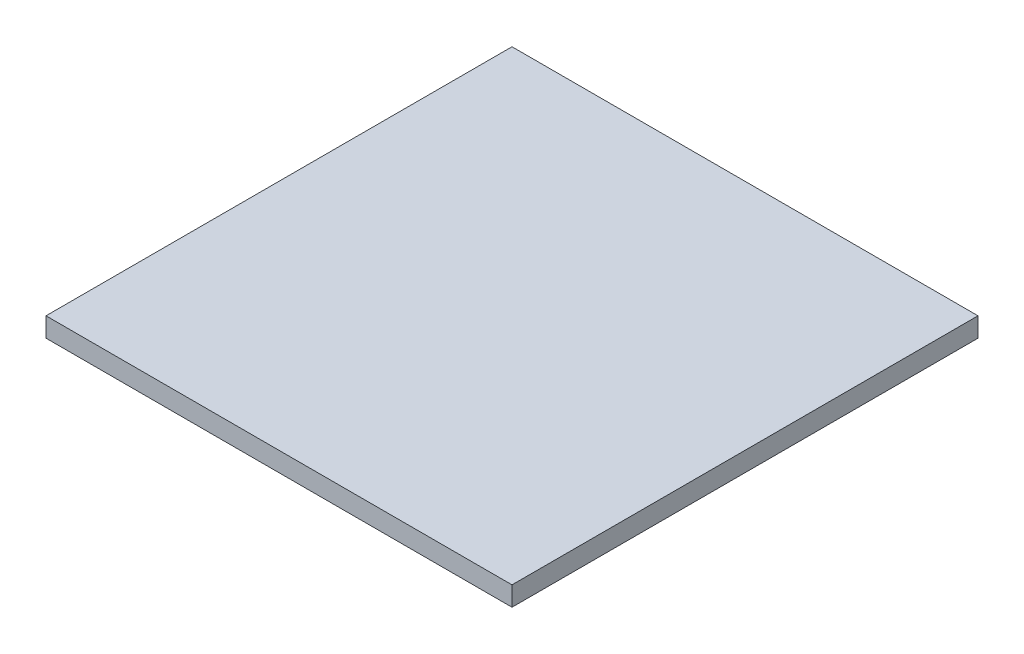
SolidWorks part; units mm, degrees
ref_plane "Front Plane" through (0, 0, 0) normal (0, 0, 1) x (1, 0, 0)
ref_plane "Top Plane" through (0, 0, 0) normal (0, 1, 0) x (1, 0, 0)
ref_plane "Right Plane" through (0, 0, 0) normal (1, 0, 0) x (0, 0, -1)
sketch "Sketch1" plane through (0, 0, 0) normal (0, 1, 0) x (1, 0, 0)
  line L0 (0, 76.2) -> (0, -76.2) construction
  line L1 (-76.2, 76.2) -> (76.2, 76.2)
  line L2 (-76.2, 76.2) -> (-76.2, -76.2)
  line L3 (-76.2, -76.2) -> (76.2, -76.2)
  line L4 (76.2, 76.2) -> (76.2, -76.2)
  line L5 (-76.2, 0) -> (76.2, 0) construction
  dimension "D1" = 152.4
extrude "Boss-Extrude1" add sketch "Sketch1" along normal blind 6.35
ref_axis "HorizontalAxis" through (83.82, 0, 0) along (-1, 0, 0)
ref_plane "VerticalPlane" through (0, 0, 0) normal (0, -0.7071, 0.7071) x (-1, 0, 0)
ref_axis "CentralAxis" through (0, 6.6675, 6.6675) along (0, -0.7071, -0.7071)
